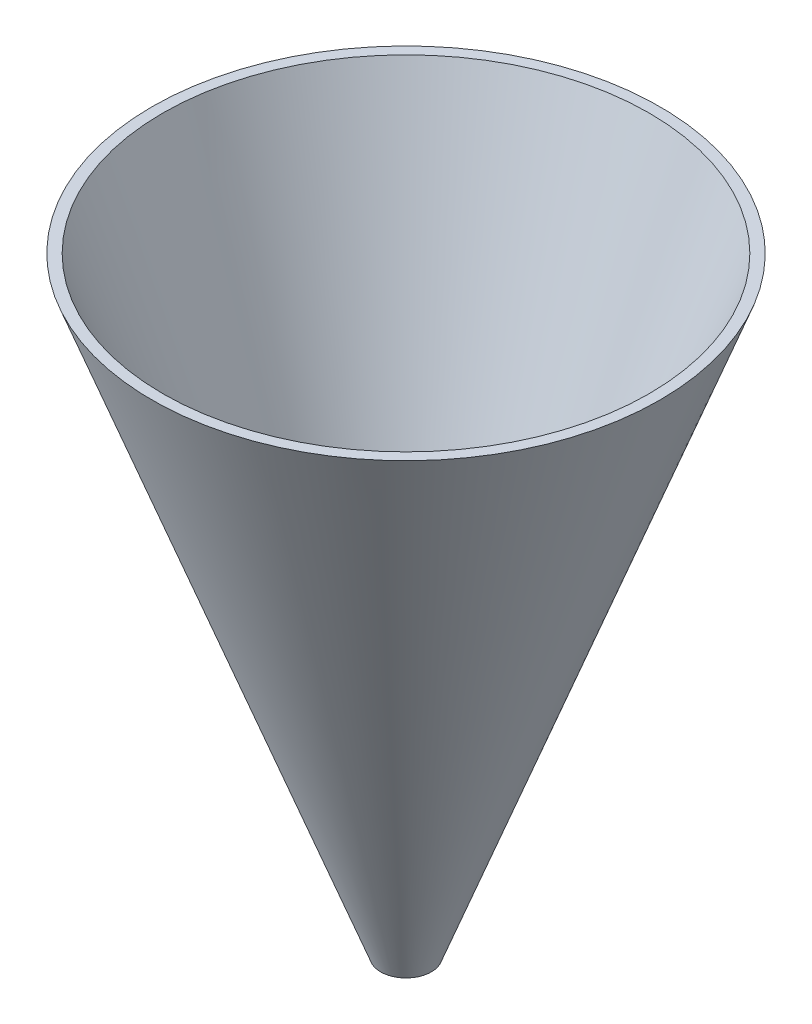
SolidWorks part; units mm, degrees
ref_plane "Front Plane" through (0, 0, 0) normal (0, 0, 1) x (1, 0, 0)
ref_plane "Top Plane" through (0, 0, 0) normal (0, 1, 0) x (1, 0, 0)
ref_plane "Right Plane" through (0, 0, 0) normal (1, 0, 0) x (0, 0, -1)
sketch "Sketch2" plane through (0, 0, 0) normal (0, 0, 1) x (1, 0, 0)
  line L0 (0, 0) -> (6.35, 0)
  line L1 (6.35, 0) -> (63.5, 152.4)
  line L2 (63.5, 152.4) -> (0, 152.4)
  line L3 (0, 152.4) -> (0, 0)
  dimension "D1" = 6.35
  dimension "D2" = 63.5
  dimension "D3" = 152.4
revolve "Revolve2" add sketch "Sketch2" angle 360 about L3
shell "Shell1" thickness 2.54 removed face at (-63.5, 152.4, 0)
sketch "Sketch3" plane through (0, 0, 0) normal (0, -1, 0) x (1, 0, 0)
  circle A0 centre (-1.778, 0) radius 1.27
  circle A1 centre (1.778, 0) radius 1.27
  dimension "D2" = 1.778
  dimension "D3" = 2.54
  dimension "D1" = 1.778
extrude "Cut-Extrude1" cut sketch "Sketch3" against normal blind 2.54
